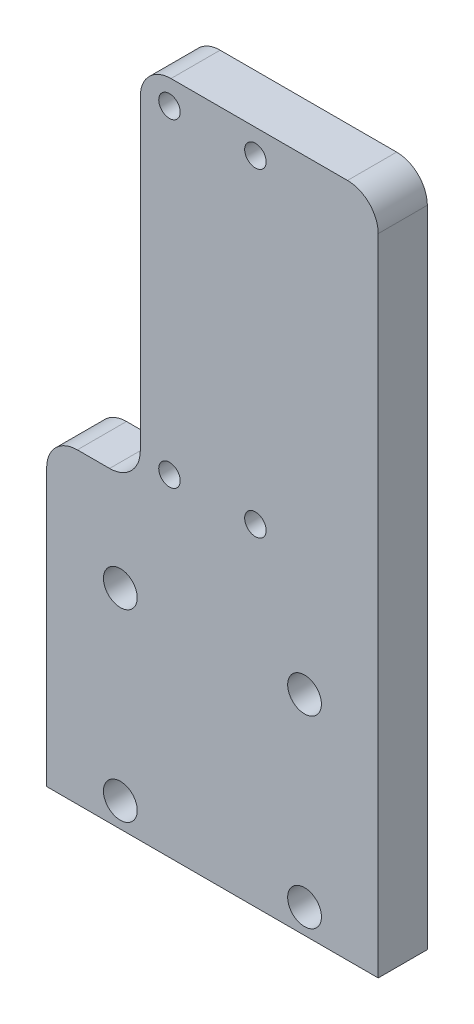
SolidWorks part; units mm, degrees
ref_plane "前视基准面" through (0, 0, 0) normal (0, 0, 1) x (1, 0, 0)
ref_plane "上视基准面" through (0, 0, 0) normal (0, 1, 0) x (1, 0, 0)
ref_plane "右视基准面" through (0, 0, 0) normal (1, 0, 0) x (0, 0, -1)
other "Configuration Table"
sketch "草图1" plane through (0, 0, 0) normal (0, 0, 1) x (1, 0, 0)
  line L0 (27, -110) -> (27, -10) construction
  line L1 (0, 0) -> (54, 0)
  line L2 (0, 0) -> (0, -110)
  line L3 (0, -110) -> (54, -110)
  line L4 (54, -52) -> (54, -110)
  line L9 (54, -52) -> (54, 0)
  circle A0 centre (12, -106) radius 2.75
  circle A1 centre (42, -106) radius 2.75
  circle A2 centre (42, -76) radius 2.75
  circle A3 centre (12, -76) radius 2.75
  dimension "D7" = 5.5
  dimension "D1" = 54
  dimension "D2" = 110
  dimension "D5" = 54
  dimension "D6" = 4
  dimension "D8" = 15
  dimension "D9" = 2
  dimension "D10" = 2
extrude "凸台-拉伸1" add sketch "草图1" along normal blind 8
sketch "草图2" plane through (0, 0, 0) normal (0, 0, -1) x (-1, 0, 0)
  line L0 (-27, 0) -> (-27, -110) construction
  line L1 (-54, 0) -> (0, 0) construction
  line L2 (0, -110) -> (-54, -110) construction
  line L3 (-15.25, 0) -> (-15.25, -60)
  line L4 (-15.25, -60) -> (0, -60)
  line L5 (0, 0) -> (0, -110) construction
  line L6 (-15.25, 0) -> (0, 0)
  line L7 (0, 0) -> (0, -60)
  dimension "D1" = 11.75
  dimension "D2" = 60
extrude "切除-拉伸1" cut sketch "草图2" against normal blind 10
fillet "圆角1" radius 5 4 edges at (15.25, 0, 4) (15.25, -60, 4) (54, 0, 4) (0, -60, 4)
sketch "草图3" plane through (0, 0, 0) normal (0, 0, -1) x (-1, 0, 0)
  circle A0 centre (-20, -4) radius 1.75
  circle A1 centre (-34, -4) radius 1.75
  circle A2 centre (-34, -56) radius 1.75
  circle A3 centre (-20, -56) radius 1.75
  dimension "D1" = 3.5
  dimension "D2" = 2
  dimension "D3" = 2
extrude "切除-拉伸2" cut sketch "草图3" against normal through all
